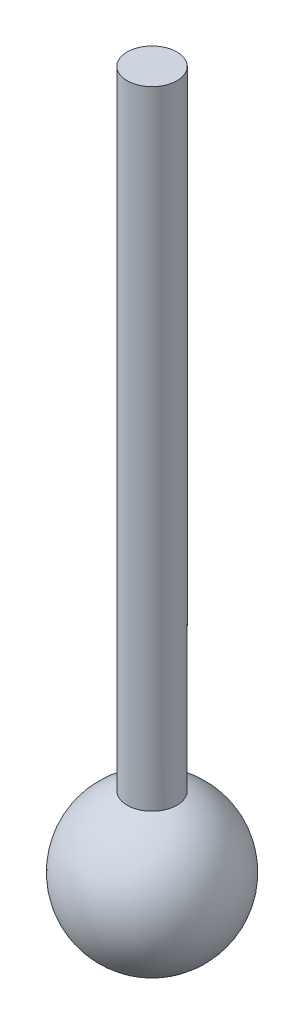
SolidWorks part; units mm, degrees
ref_plane "Front Plane" through (0, 0, 0) normal (1, 0, 0) x (0, 1, 0)
ref_plane "Top Plane" through (0, 0, 0) normal (0, 0, 1) x (0, 1, 0)
ref_plane "Right Plane" through (0, 0, 0) normal (0, 1, 0) x (-1, 0, 0)
sketch "Sketch1" plane through (0, 0, 0) normal (1, 0, 0) x (0, 1, 0)
  line L0 (0, 0) -> (158.75, 0)
  line L1 (158.75, 0) -> (158.75, 6.35)
  line L2 (158.75, 6.35) -> (-1.0895, 6.35)
  line L3 (-19.05, 0) -> (0, 0)
  line L4 (-19.05, 0) -> (-38.1, 0)
  circle A0 centre (-19.05, 0) radius 19.05
  dimension "D3" = 38.1
  dimension "D1" = 6.35
  dimension "D2" = 177.8
revolve "Revolve1" add sketch "Sketch1" angle 360 about L0 region at (0, 79.1952, 3.1786) region at (0, -19.05, 8.0851)
